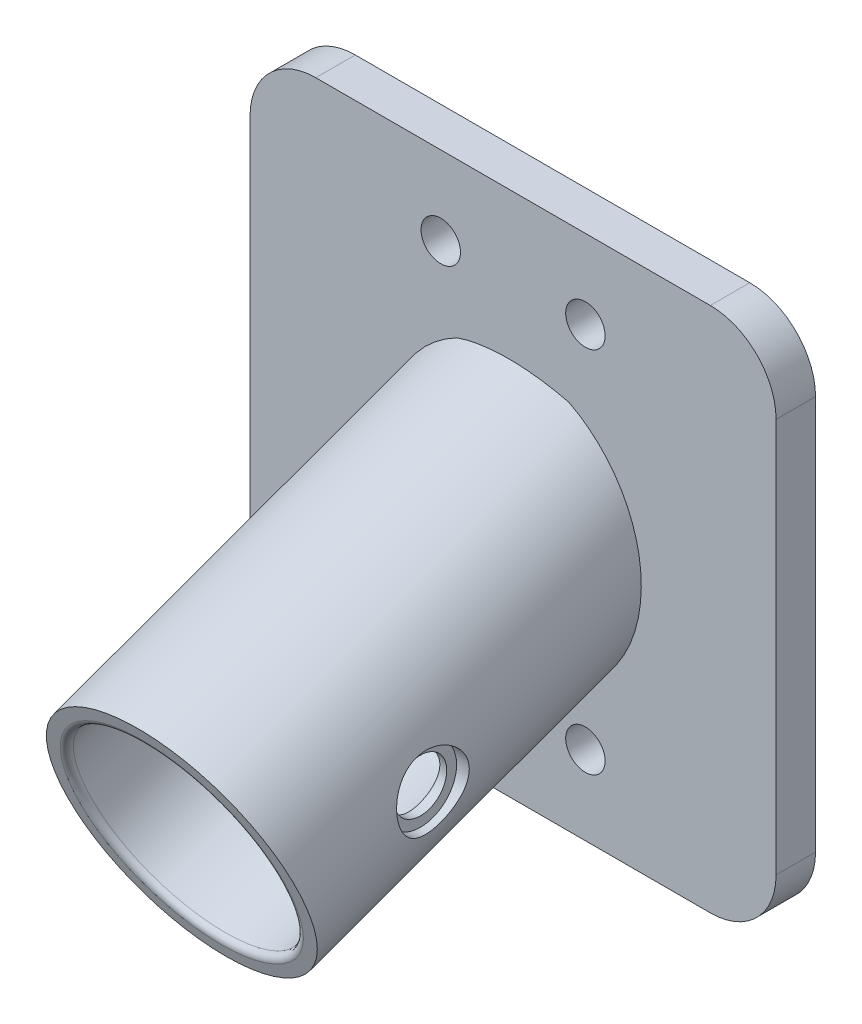
SolidWorks part; units mm, degrees
ref_plane "前基準面" through (0, 0, 0) normal (0, 0, 1) x (1, 0, 0)
ref_plane "上基準面" through (0, 0, 0) normal (0, 1, 0) x (1, 0, 0)
ref_plane "右基準面" through (0, 0, 0) normal (1, 0, 0) x (0, 0, -1)
sketch "草圖1" plane through (0, 0, 0) normal (0, 0, 1) x (1, 0, 0)
  line L1 (-15, 20) -> (15, 20)
  line L2 (-20, 15) -> (-20, -15)
  line L3 (-15, -20) -> (15, -20)
  line L4 (20, 15) -> (20, -15)
  line L5 (-20, 20) -> (20, -20) construction
  line L6 (-20, -20) -> (20, 20) construction
  arc A0 (15, -20) -> (20, -15) centre (15, -15) ccw
  arc A1 (-20, -15) -> (-15, -20) centre (-15, -15) ccw
  arc A2 (15, 20) -> (20, 15) centre (15, 15) cw
  arc A3 (-15, 20) -> (-20, 15) centre (-15, 15) ccw
  point P0 (0, 0)
  dimension "D2" = 5
  dimension "D1" = 40
extrude "填料-伸長1" add sketch "草圖1" along normal blind 3
ref_axis "基準軸1" through (-22, 0, 0) along (1, 0, 0)
ref_plane "平面1" through (0, 0, 0) normal (0, -0.342, 0.9397) x (1, 0, 0)
sketch "草圖2" plane through (0, 0, 0) normal (0, 0, 1) x (1, 0, 0)
  line L0 (-1000, 0) -> (49000, 0) construction
  line L1 (0, -1000) -> (0, 49000) construction
  line L2 (-1013.5593, 14) -> (48986.4407, 14)
  line L3 (-1013.5593, -14) -> (48986.4407, -14)
  line L4 (-5.5, -984.1658) -> (-5.5, 49015.8342)
  line L5 (5.5, -984.1658) -> (5.5, 49015.8342)
  line L6 (15, 20) -> (-15, 20) construction
  line L7 (-15, -20) -> (15, -20) construction
  circle A0 centre (-5.5, 14) radius 1.5
  circle A1 centre (5.5, 14) radius 1.5
  circle A2 centre (5.5, -14) radius 1.5
  circle A3 centre (-5.5, -14) radius 1.5
  dimension "D1" = 3
  dimension "D2" = 6
  dimension "D3" = 6
  dimension "D4" = 11
extrude "除料-伸長2" cut sketch "草圖2" against normal through all and the other way through all
sketch "草圖3" plane through (0, 0, 0) normal (0, -0.342, 0.9397) x (1, 0, 0)
  circle A0 centre (0, 0) radius 9.75
  circle A1 centre (0, 0) radius 8.25
  dimension "D1" = 16.5
  dimension "D2" = 19.5
extrude "填料-伸長2" add sketch "草圖3" along normal blind 30
sketch "草圖4" plane through (0, 0, 0) normal (1, 0, 0) x (0, 0, -1)
  line L1 (0, 20) -> (10.0939, 20)
  line L2 (0, 20) -> (0, -19.9792)
  line L3 (0, -19.9792) -> (10.0939, -19.9792)
  line L4 (10.0939, 20) -> (10.0939, -19.9792)
extrude "除料-伸長3" cut sketch "草圖4" against normal mid plane 25
sketch "草圖5" plane through (0, 0, 0) normal (1, 0, 0) x (0, 0, -1)
  line L0 (-23.4923, -8.5505) -> (46961.1387, 17092.4567) construction
  line L1 (-31.5255, -1.0986) -> (-24.8561, -19.4226) construction
  circle A0 centre (-18.7939, -6.8404) radius 2
  point P4 (-28.1908, -10.2606)
  dimension "D2" = 4
  dimension "D1" = 20
extrude "除料-伸長4" cut sketch "草圖5" against normal through all both and the other way through all
ref_plane "平面2" through (9.75, 0, 0) normal (1, 0, 0) x (0, 0, -1)
sketch "草圖6" plane through (9.75, 0, 0) normal (1, 0, 0) x (0, 0, -1)
  circle A0 centre (-18.7939, -6.8404) radius 2.75
  dimension "D1" = 5.5
extrude "除料-伸長5" cut sketch "草圖6" against normal blind 1
ref_plane "平面3" through (-9.75, 0, 0) normal (1, 0, 0) x (0, 0, -1)
sketch "草圖7" plane through (-9.75, 0, 0) normal (1, 0, 0) x (0, 0, -1)
  line L0 (-24.8561, -19.4226) -> (-3, -11.4676) construction
  line L1 (-15.9191, -9.2526) -> (-15.2674, -5.5569)
  line L2 (-15.2674, -5.5569) -> (-18.1422, -3.1446)
  line L3 (-18.1422, -3.1446) -> (-21.6686, -4.4282)
  line L4 (-21.6686, -4.4282) -> (-22.3203, -8.1239)
  line L5 (-22.3203, -8.1239) -> (-19.4455, -10.5362)
  line L6 (-19.4455, -10.5362) -> (-15.9191, -9.2526)
  circle A0 centre (-18.7939, -6.8404) radius 3.25 construction
  dimension "D1" = 6.5
extrude "除料-伸長6" cut sketch "草圖7" along normal blind 1
fillet "圓角1" radius 0.5 1 edges at (0, -18.0131, 25.3691)
